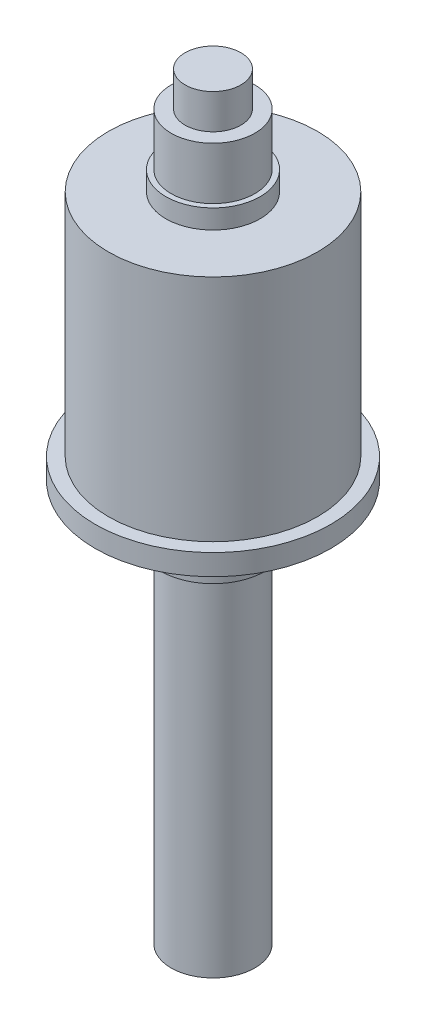
SolidWorks part; units mm, degrees
material "AISI 1035 Steel (SS)"
ref_plane "Front Plane" through (0, 0, 0) normal (0, 0, 1) x (1, 0, 0)
ref_plane "Top Plane" through (0, 0, 0) normal (0, 1, 0) x (1, 0, 0)
ref_plane "Right Plane" through (0, 0, 0) normal (1, 0, 0) x (0, 0, -1)
sketch "Sketch2" plane through (0, 0, 0) normal (0, 0, 1) x (1, 0, 0)
  line L0 (0, 40.0334) -> (0, -27.2464) construction
  line L11 (0, 0) -> (-4, 0)
  line L12 (-4, 0) -> (-4, -5)
  line L13 (-4, -5) -> (-6, -5)
  line L14 (-6, -5) -> (-6, -12.5)
  line L15 (-6, -12.5) -> (-6.75, -12.5)
  line L16 (-6.75, -12.5) -> (-6.75, -15.25)
  line L17 (-6.75, -15.25) -> (-14.9815, -15.25)
  line L18 (-14.9815, -15.25) -> (-14.9815, -48.11)
  line L26 (0, -108.61) -> (0, 0)
  line L28 (-16.8815, -51.11) -> (-16.8815, -48.11)
  line L29 (-16.8815, -48.11) -> (-14.9815, -48.11)
  line L30 (-16.8815, -51.11) -> (-8.25, -51.11)
  line L31 (-8.25, -51.11) -> (-8.25, -53.61)
  line L32 (-14.9815, -48.11) -> (-14.9815, -51.11) construction
  line L33 (-8.25, -53.61) -> (-7.5, -53.61)
  line L34 (-7.5, -53.61) -> (-7.5, -58.61)
  line L35 (-7.5, -58.61) -> (-6, -58.61)
  line L36 (-6, -58.61) -> (-6, -108.61)
  line L37 (-6, -108.61) -> (0, -108.61)
  dimension "D1" = 4
  dimension "D2" = 5
  dimension "D3" = 6
  dimension "D4" = 7.5
  dimension "D5" = 6.75
  dimension "D6" = 2.75
  dimension "D7" = 14.9815
  dimension "D8" = 32.86
  dimension "D10" = 3
  dimension "D11" = 8.25
  dimension "D12" = 2.5
  dimension "D13" = 7.5
  dimension "D14" = 5
  dimension "D15" = 6
  dimension "D16" = 50
  dimension "D9" = 1.9
revolve "Revolve1" add sketch "Sketch2" angle 360 about L0
equation "\"Stator_OD\"= 60'No Tolerance given"
equation "\"A\"=35.81 'taken off spec sheet for 06808 (A)"
equation "\"Rotor_ID\"= 30'No Tolerance Given"
equation "\"back_bearing_Thickness\"= 5'-0.12"
equation "\"back_bearing_OD\"= 24'-0.009 https://www.mcmaster.com/5972K155/"
equation "\"Stator_Gap\"= 0.0375'+- 0.0125 (From 1.3.3.1 Kollmorgen manual)"
equation "\"Back_mount_hole\"= 1.75'To be tapped to M2 (USE LOCKTITE)"
equation "\"facePlate_Mount_Hole\"= 2.75'To be tapped to M3"
equation "\"final_shaftD\"= 12'To fit in harmonic"
equation "\"back_bearing_ID\"= 15'"
equation "\"rotor_shaftD\"= \"Rotor_ID\" - (\"rotor-shaft_gap\")*2'"
equation "\"back_bearing_IDOD\"= 16.5'measured off CAD, actually 16.75, but rounded down to nicer number"
equation "\"final_shaftL\"= 50'random length. Idk"
equation "\"D1@Sketch2\"=4"
equation "\"D3@Sketch2\"=\"front_bearing_ID\"/2"
equation "\"D4@Sketch2\" = \"front_bearing_Thickness\" + 2.5"
equation "\"D5@Sketch2\"=\"front_bearing_IDOD\" / 2"
equation "\"D8@Sketch2\"=\"rotor_height\""
equation "\"front_bearing_ID\"= 12'https://www.mcmaster.com/5972K154/"
equation "\"front_bearing_OD\"= 21'-0.009"
equation "\"front_bearing_IDOD\"= 13.5'Measured off CAD. Actually 13.75, but rounded down"
equation "\"front_bearing_Thickness\"= 5'-0.12"
equation "\"rotor_thickness\"= 2.4'measured off CAD"
equation "\"rotor_height\"= 32.86'+-0.075 taken off spec sheet for 06826 (C)"
equation "\"D11@Sketch2\"=\"back_bearing_IDOD\"/2"
equation "\"D13@Sketch2\"=\"back_bearing_ID\"/2"
equation "\"D14@Sketch2\"=\"back_bearing_Thickness\""
equation "\"D15@Sketch2\"=\"final_shaftD\"/2"
equation "\"D16@Sketch2\"=\"final_shaftL\""
equation "\"D9@Sketch2\"=\"rotor_thickness\"-0.5"
equation "\"rotor-shaft_gap\" = 0.0185 '+-0.0065 (from manual)"
equation "\"D7@Sketch2\"=\"Rotor_ID\"/2-\"rotor-shaft_gap\""
